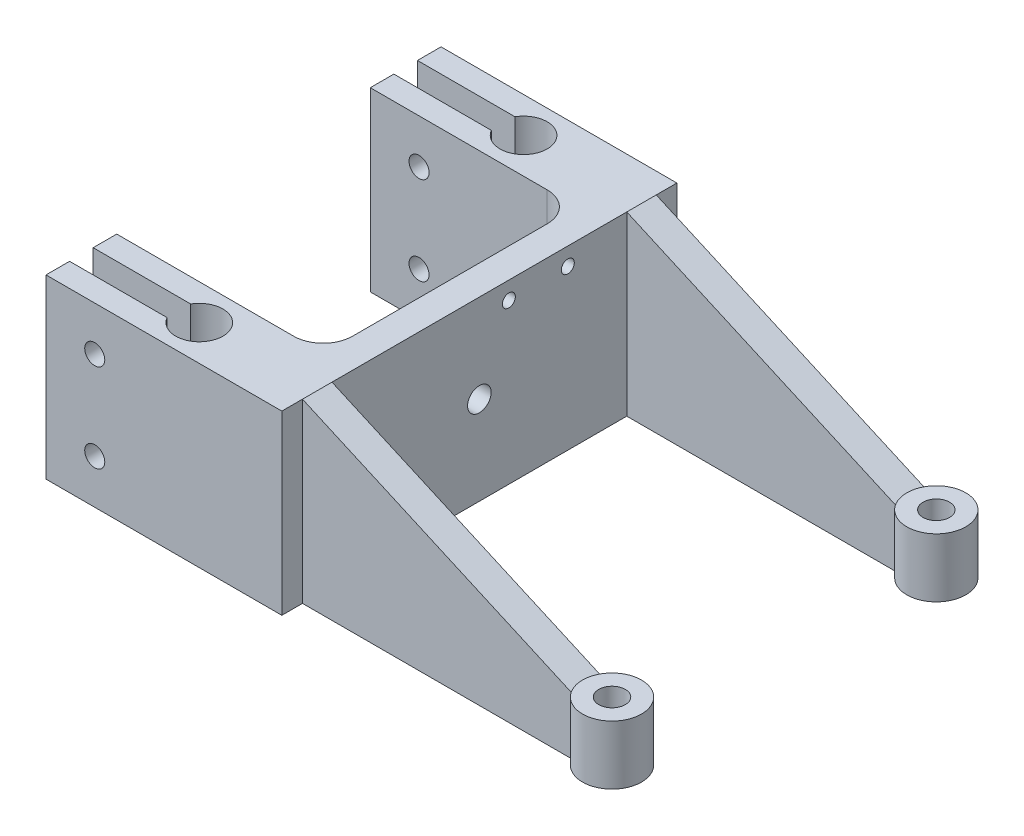
SolidWorks part; units mm, degrees
ref_plane "Front Plane" through (0, 0, 0) normal (0, 0, 1) x (1, 0, 0)
ref_plane "Top Plane" through (0, 0, 0) normal (0, 1, 0) x (1, 0, 0)
ref_plane "Right Plane" through (0, 0, 0) normal (1, 0, 0) x (0, 0, -1)
sketch "Sketch1" plane through (0, 0, 0) normal (0, 1, 0) x (1, 0, 0)
  line L0 (0, 0) -> (-33.9198, 0) construction
  line L1 (-5, 0) -> (0, 0)
  line L2 (36, 0) -> (36, 17.5) construction
  line L3 (36, 17.5) -> (0, 17.5) construction
  line L4 (0, 25) -> (45.6699, 25)
  line L5 (0, 25) -> (0, 30) construction
  line L6 (50, 27.5) -> (-40, 27.5) construction
  line L7 (0, 30) -> (45.6699, 30)
  line L8 (0, 0) -> (0, 33.5)
  line L9 (0, 33.5) -> (-40, 33.5)
  line L10 (-10, 21.5) -> (-40, 21.5)
  line L11 (-40, 33.5) -> (-40, 29.5)
  line L12 (-5, 16.5) -> (-5, 0)
  line L13 (-40, 25.5) -> (-40, 21.5)
  line L14 (-40, 25.5) -> (-23.4641, 25.5)
  line L15 (-40, 29.5) -> (-40, 25.5) construction
  line L16 (-40, 29.5) -> (-23.4641, 29.5)
  circle A0 centre (50, 27.5) radius 2.25
  circle A1 centre (50, 27.5) radius 5
  arc A2 (-23.4641, 25.5) -> (-23.4641, 29.5) centre (-20, 27.5) ccw
  arc A3 (-5, 16.5) -> (-10, 21.5) centre (-10, 16.5) ccw
  circle A4 centre (-5, 27.5) radius 2.25
  point P0 (0, 0)
  dimension "D4" = 4.5
  dimension "D5" = 10
  dimension "D9" = 8
  dimension "D14" = 5
  dimension "D15" = 55
  dimension "D1" = 35
  dimension "D2" = 36
  dimension "D3" = 55
  dimension "D6" = 12
  dimension "D7" = 5
  dimension "D8" = 40
  dimension "D10" = 5
  dimension "D11" = 15
  dimension "D12" = 4
  dimension "D13" = 50
extrude "Boss-Extrude1" add sketch "Sketch1" along normal blind 30 contours A3 L12 L1 L8 L9 L11 L16 A2 L14 L13 L10 | A4 region at (-14.6151, 0, -23.5199) region at (-5, 0, -27.5)
extrude "Boss-Extrude2" add sketch "Sketch1<3>" along normal blind 10 separate body contours A1 A0 region at (45.1414, 0, -27.5)
sketch "Sketch1<3>" plane through (0, 0, 0) normal (0, 1, 0) x (1, 0, 0) same geometry as "Sketch1"
ref_plane "Plane1" through (0, 0, -27.5) normal (0, 0, 1) x (1, 0, 0)
sketch "Sketch2" plane through (0, 0, 0) normal (0, 0, 1) x (1, 0, 0)
  line L0 (0, 30) -> (47.75, 8.7778)
  line L1 (0, -16.5) -> (0, 16.5) construction
  line L2 (-10, 0) -> (-40, 0) construction
  line L3 (47.75, 8.7778) -> (47.75, 0)
  line L4 (47.75, 0) -> (0, 0)
  line L5 (0, 0) -> (0, 30)
  line L6 (-23.4641, 15) -> (-40, 15)
  line L7 (-23.4641, 30) -> (-23.4641, 0) construction
  line L8 (-31.7321, 30) -> (-31.7321, 22.5) construction
  line L9 (-10, 30) -> (-40, 30) construction
  line L10 (-31.7321, 22.5) -> (-31.7321, 15)
  line L11 (-31.7321, 15) -> (-31.7321, 7.5)
  line L12 (-40, 30) -> (-40, 0) construction
  line L14 (-31.7321, 7.5) -> (-31.7321, 0)
  circle A1 centre (-31.7321, 7.5) radius 1.7
  circle A2 centre (-31.7321, 22.5) radius 1.7
  point P6 (45, 10)
  dimension "D2" = 3.4
extrude "Boss-Extrude3" add sketch "Sketch2" along normal mid plane 5 from surface contours L0 L3 L4 L5 starting at plane "Plane1"
extrude "Cut-Extrude2" cut sketch "Sketch1<4>" along normal blind 10 contours A4
sketch "Sketch1<4>" plane through (0, 0, 0) normal (0, 1, 0) x (1, 0, 0) same geometry as "Sketch1"
extrude "Cut-Extrude3" cut sketch "Sketch2<3>" against normal up to surface (33.5 mm away) from surface contours A2 | A1 up to face at (-20, 15, -33.5) starting at face at (-25, 15, -21.5)
sketch "Sketch2<3>" plane through (0, 0, 0) normal (0, 0, 1) x (1, 0, 0) same geometry as "Sketch2"
mirror "Mirror1" about plane through (0, 0, 0) normal (0, 0, 1) of bodies 107 103
sketch "Sketch3" plane through (-5, 0, 0) normal (-1, 0, 0) x (0, 0, 1)
  line L0 (-16.5, 30) -> (16.5, 30) construction
  circle A0 centre (0, 15) radius 2
  circle A1 centre (-15, 27) radius 1.1
  circle A2 centre (-5, 27) radius 1.1
  dimension "D1" = 4
  dimension "D5" = 2.2
  dimension "D2" = 15
  dimension "D3" = 5
  dimension "D4" = 10
  dimension "D6" = 3
extrude "Cut-Extrude4" cut sketch "Sketch3" against normal up to next
equation "\"SmoothRodDiameter\"=8"
equation "\"D9@Sketch1\"=\"SmoothRodDiameter\""
equation "\"D6@Sketch1\"=1.5*\"SmoothRodDiameter''''''''''"
equation "\"D12@Sketch1\"=.5*\"SmoothRodDiameter\""
equation "\"IdlerEndHeight\"=30"
equation "\"D1@Boss-Extrude1\"=\"IdlerEndHeight\""
equation "\"WebWidth\"=5"
equation "\"D7@Sketch1\"=\"WebWidth\""
equation "\"D1@Boss-Extrude3\"=\"WebWidth\""
equation "\"SmoothRodSpacing\"=55"
equation "\"D3@Sketch1\"=\"SmoothRodSpacing\""
